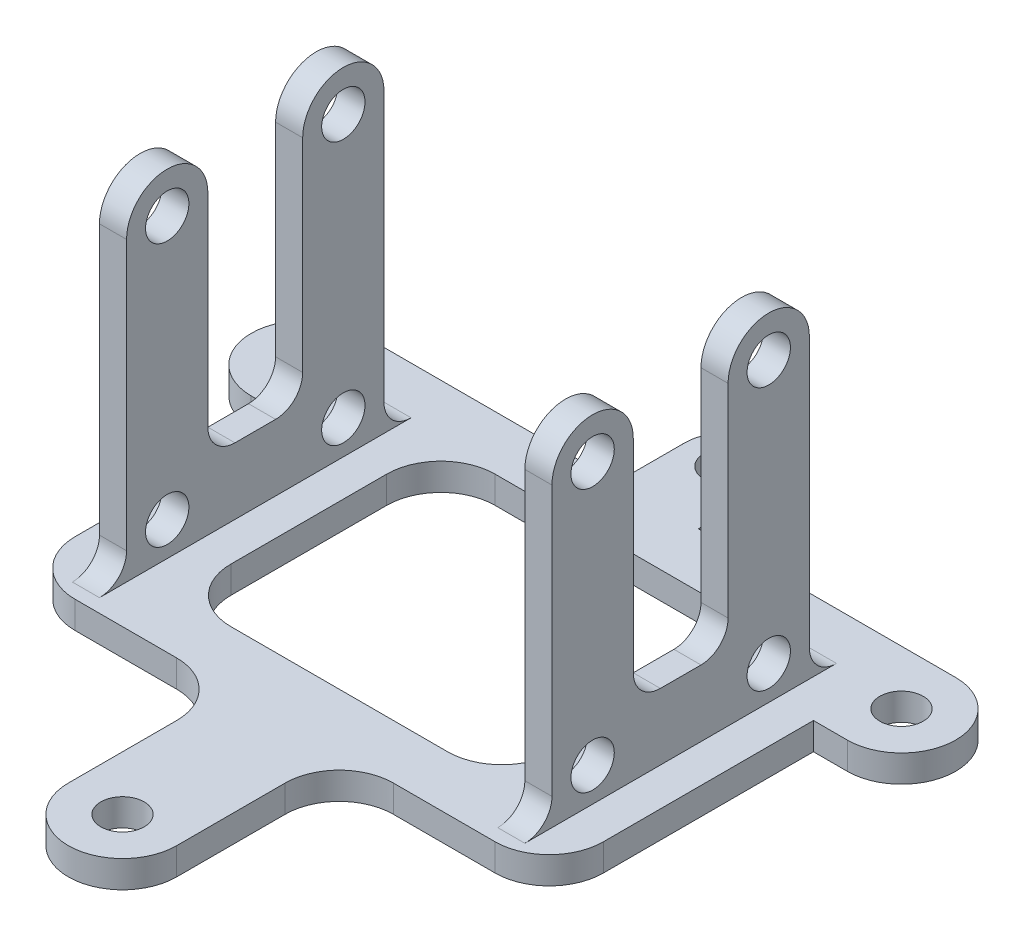
SolidWorks part; units mm, degrees
ref_plane "Front Plane" through (0, 0, 0) normal (0, 0, 1) x (1, 0, 0)
ref_plane "Top Plane" through (0, 0, 0) normal (0, 1, 0) x (1, 0, 0)
ref_plane "Right Plane" through (0, 0, 0) normal (1, 0, 0) x (0, 0, -1)
sketch "Sketch1" plane through (0, 0, 0) normal (0, 1, 0) x (1, 0, 0)
  line L2 (26, -5) -> (26, -15)
  line L3 (4, 0) -> (4, -1)
  line L4 (22, -1) -> (4, -1)
  line L5 (-4, -1) -> (-4, 0)
  line L7 (22, -19) -> (4, -19)
  line L8 (4, -30) -> (4, -19)
  line L9 (-4, -30) -> (-4, -19)
  line L10 (-22, -1) -> (-4, -1)
  line L11 (-4, 0) -> (-4, -1)
  line L12 (-26, -5) -> (-26, -15)
  line L13 (-4, -45) -> (-4, -30)
  line L14 (-22, -19) -> (-4, -19)
  line L15 (4, -1) -> (4, 0)
  line L16 (4, -45) -> (4, -30)
  line L17 (-1.6, -30) -> (-1.6, -45)
  line L19 (1.6, -30) -> (1.6, -45)
  circle A0 centre (0, 0) radius 1.6
  arc A1 (4, 0) -> (-4, 0) centre (0, 0) ccw
  circle A2 centre (22, -5) radius 1.6
  arc A3 (26, -5) -> (22, -1) centre (22, -5) ccw
  circle A4 centre (22, -15) radius 1.6
  arc A5 (22, -19) -> (26, -15) centre (22, -15) ccw
  arc A6 (1.6, -30) -> (-1.6, -30) centre (0, -30) ccw
  arc A8 (-22, -19) -> (-26, -15) centre (-22, -15) cw
  circle A9 centre (-22, -15) radius 1.6
  arc A10 (-26, -5) -> (-22, -1) centre (-22, -5) cw
  circle A11 centre (-22, -5) radius 1.6
  arc A12 (-4, -45) -> (4, -45) centre (0, -45) ccw
  arc A13 (-1.6, -45) -> (1.6, -45) centre (0, -45) ccw
extrude "Boss-Extrude1" add sketch "Sketch1" along normal blind 2 contours L13 A12 L16 L8 L7 A5 L2 A3 L4 L3 A1 L5 L10 A10 L12 A8 L14 L9 A13 L17 A6 L19 A11 A0 A2 A4 A9 region at (0, 0, 13.3577)
sketch "Sketch2" plane through (0, 2, 0) normal (0, 1, 0) x (1, 0, 0)
  line L0 (0, 0) -> (0, 3)
  line L1 (-4, 0) -> (-4, 3)
  line L2 (4, 0) -> (4, 3)
  circle A0 centre (0, 3) radius 4
  circle A1 centre (0, 0) radius 4
  circle A2 centre (0, 3) radius 1.6
extrude "Boss-Extrude3" add sketch "Sketch2" against normal up to surface (2 mm away) contours A2 A0 | A0 L2 | A0 L1 | A1 region at (-3.913, 2, -1.5) region at (0, 2, -4.7483) region at (3.913, 2, -1.5) up to face at (0, 0, 37.5)
sketch "Sketch4" plane through (0, 2, 0) normal (0, 1, 0) x (1, 0, 0)
  circle A0 centre (0, 3) radius 1.6
extrude "Cut-Extrude2" cut sketch "Sketch4" against normal blind 4
sketch "Sketch5" plane through (0, 2, 0) normal (0, 1, 0) x (1, 0, 0)
  line L0 (-4, -1) -> (4, -1)
  line L1 (-4, -1) -> (-11.9576, 14.4075)
  line L2 (-11.9576, 14.4075) -> (9.1218, 12.8952)
  line L3 (9.1218, 12.8952) -> (4, -1)
extrude "Cut-Extrude3" cut sketch "Sketch5" against normal blind 10
sketch "Sketch6" plane through (0, 2, 0) normal (0, 1, 0) x (1, 0, 0)
  line L0 (22, -1) -> (-22, -1) construction
  circle A0 centre (0, -1) radius 3
  circle A1 centre (0, -1) radius 1.6
extrude "Boss-Extrude4" add sketch "Sketch6" against normal up to surface (2 mm away) up to face at (0, 0, 37.5)
sketch "Sketch7" plane through (0, 2, 0) normal (0, 1, 0) x (1, 0, 0)
  line L0 (1.6, -1) -> (-1.6, -1) construction
  circle A0 centre (0, -1) radius 1.6
extrude "Cut-Extrude4" cut sketch "Sketch7" against normal blind 10
sketch "Sketch8" plane through (0, 2, 0) normal (0, 1, 0) x (1, 0, 0)
  line L0 (-18, -5) -> (-18, -15)
  line L1 (18, -5) -> (18, -15)
  line L2 (18, -15) -> (-18, -15)
  line L3 (-18, -5) -> (18, -5)
  circle A0 centre (-22, -5) radius 4
  circle A1 centre (-22, -15) radius 4
  circle A2 centre (22, -15) radius 4
  circle A3 centre (22, -5) radius 4
extrude "Cut-Extrude6" cut sketch "Sketch8" against normal blind 9.5 contours L3 L0 L2 L1 region at (0, 2, 10)
fillet "Fillet3" radius 3 4 edges at (18, 1, 5) (18, 1, 15) (-18, 1, 15) (-18, 1, 5)
sketch "Sketch9" plane through (0, 2, 0) normal (0, 1, 0) x (1, 0, 0)
  circle A0 centre (0, -1) radius 1.6
extrude "Boss-Extrude5" add sketch "Sketch9" against normal up to surface (2 mm away) up to face at (0, 0, 15.0714)
sketch "Sketch10" plane through (0, 2, 0) normal (0, 1, 0) x (1, 0, 0)
  line L0 (3, -1) -> (3, 3)
  line L1 (3, -1) -> (-3, -1)
  line L2 (-3, -1) -> (-3, 3)
  arc A0 (3, 3) -> (-3, 3) centre (0, 3) ccw
  circle A1 centre (0, 3) radius 1.6
extrude "Boss-Extrude6" add sketch "Sketch10" against normal up to surface (2 mm away) up to face at (0, 0, 15.0714)
sketch "Sketch11" plane through (0, 2, 0) normal (0, 1, 0) x (1, 0, 0)
  circle A0 centre (0, 3) radius 1.6
extrude "Cut-Extrude7" cut sketch "Sketch11" against normal blind 10
sketch "Sketch12" plane through (0, 2, 0) normal (0, 1, 0) x (1, 0, 0)
  line L1 (-3, 3) -> (-3, 4)
  line L3 (3, 4) -> (3, 3)
  line L4 (3, 3) -> (2.8284, 3)
  line L5 (-2.8284, 3) -> (-3, 3)
  arc A0 (-2.8284, 3) -> (2.8284, 3) centre (0, 4) ccw
  arc A1 (3, 4) -> (-3, 4) centre (0, 4) ccw
extrude "Boss-Extrude7" add sketch "Sketch12" against normal up to surface (2 mm away) up to face at (0, 0, 12.8125)
sketch "Sketch13" plane through (0, 2, 0) normal (0, 1, 0) x (1, 0, 0)
  circle A0 centre (0, 4) radius 1.6
extrude "Cut-Extrude9" cut sketch "Sketch13" against normal blind 5.5
sketch "Sketch14" plane through (0, 2, 0) normal (0, 1, 0) x (1, 0, 0)
sketch "Sketch15" plane through (0, 2, 0) normal (0, 1, 0) x (1, 0, 0)
  line L0 (-4, -45) -> (-4, -23.9538)
  line L1 (-4, -23.9538) -> (4, -23.9538)
  line L2 (4, -23.9538) -> (4, -45)
  arc A1 (-4, -45) -> (4, -45) centre (0, -45) ccw
extrude "Boss-Extrude8" add sketch "Sketch15" against normal up to surface (2 mm away) up to face at (0, 0, -2.4)
sketch "Sketch16" plane through (0, 2, 0) normal (0, 1, 0) x (1, 0, 0)
  circle A0 centre (0, -45) radius 1.6
  circle A1 centre (0, -36) radius 1.6
extrude "Cut-Extrude10" cut sketch "Sketch16" against normal blind 10
sketch "Sketch17" plane through (0, 2, 0) normal (0, 1, 0) x (1, 0, 0)
  circle A0 centre (0, -36) radius 2.8849
extrude "Boss-Extrude9" add sketch "Sketch17" against normal blind 1
sketch "Sketch18" plane through (0, 1, 0) normal (0, -1, 0) x (-1, 0, 0)
  circle A0 centre (0, -36) radius 1.6
extrude "Boss-Extrude10" add sketch "Sketch18" along normal blind 3
sketch "Sketch19" plane through (0, -2, 0) normal (0, -1, 0) x (-1, 0, 0)
  circle A0 centre (0, -36) radius 1.6
  circle A1 centre (0, -36) radius 1.5
extrude "Cut-Extrude11" cut sketch "Sketch19" against normal up to surface (2 mm away) up to face at (0, 0, 46.6)
sketch "Sketch20" plane through (0, 0, 0) normal (0, -1, 0) x (-1, 0, 0)
  circle A0 centre (0, -40.5) radius 1.6
extrude "Cut-Extrude12" cut sketch "Sketch20" against normal blind 10
sketch "Sketch21" plane through (0, 0, 0) normal (0, -1, 0) x (-1, 0, 0)
  circle A1 centre (0, -36) radius 1.5
extrude "Cut-Extrude13" cut sketch "Sketch21" along normal blind 8.5
sketch "Sketch22" plane through (0, 2, 0) normal (0, 1, 0) x (1, 0, 0)
  line L1 (-16.5, -15) -> (-16.5, -6.5)
  line L2 (-16.5, -6.5) -> (-14.6649, -6.5)
  line L3 (-14.6649, -6.5) -> (-14.6649, -25.5)
  line L4 (-14.6649, -25.5) -> (-16.5, -25.5)
  line L5 (-16.5, -25.5) -> (-16.5, -15)
  line L7 (16.5, -25.5) -> (16.5, -15)
  line L8 (14.5, -25.5) -> (16.5, -25.5)
  line L9 (14.5, -6.5) -> (14.5, -25.5)
  line L10 (16.5, -6.5) -> (14.5, -6.5)
  line L11 (16.5, -15) -> (16.5, -6.5)
extrude "Boss-Extrude12" add sketch "Sketch22" along normal blind 25 and the other way blind 2
sketch "Sketch23" plane through (16.5, 0, 0) normal (1, 0, 0) x (0, 0, -1)
  line L0 (-25.5, 2) -> (-22.5, 2)
  line L1 (-25.5, 0) -> (-25.5, 27) construction
  line L2 (-25.5, 2) -> (-25.5, 0)
  line L4 (-22.5, 2) -> (-22.5, 4.5)
  line L5 (-22.5, 4.5) -> (-22.5, 23.9)
  line L6 (-22.5, 23.9) -> (-19.5, 23.9)
  line L7 (-19.5, 23.9) -> (-19.5, 6.9)
  line L8 (-19.5, 6.9) -> (-12.5, 6.9)
  line L9 (-12.5, 6.9) -> (-12.5, 23.9)
  line L10 (-25.5, 23.9) -> (-25.5, 2)
  line L11 (-6.5, 23.9) -> (-6.6, 2)
  line L12 (-6.6, 2) -> (-22.5, 2)
  line L13 (-12.5, 23.9) -> (-9.5, 23.9)
  circle A0 centre (-22.5, 23.9) radius 3
  circle A1 centre (-9.5, 23.9) radius 3
  line M9 (-6.5, 0) -> (-6.5, 27)
  line M10 (-6.5, 27) -> (-25.5, 27)
  line M11 (-25.5, 27) -> (-25.5, 0)
extrude "Cut-Extrude14" cut sketch "Sketch23" against normal blind 48 contours A1 A0 L7 L8 L9 M9 M10 M11 region at (16.5, 17.5094, 16)
sketch "Sketch24" plane through (16.5, 0, 0) normal (1, 0, 0) x (0, 0, -1)
  circle A0 centre (-22.5, 23.9) radius 1.6
  circle A1 centre (-9.5, 23.9) radius 1.6
  circle A2 centre (-22.5, 4.5) radius 1.6
  circle A3 centre (-9.5, 4.5) radius 1.6
extrude "Cut-Extrude15" cut sketch "Sketch24" against normal blind 48
sketch "Sketch25" plane through (0, 0, 0) normal (0, -1, 0) x (-1, 0, 0)
  line L0 (14.6649, -6.5) -> (14.6649, -3.5087)
  line L1 (14.6649, -3.5087) -> (19.1284, -3.5087)
  line L2 (19.1284, -3.5087) -> (19.1284, -15.8565)
  line L3 (19.1284, -15.8565) -> (14.6649, -15.8565)
  line L4 (14.6649, -15.8565) -> (14.6649, -6.5)
  line L5 (-14.5, -6.7838) -> (-14.5, -16.6973)
  line L6 (-14.5, -6.5) -> (-14.5, -15) construction
  line L7 (-14.5, -16.6973) -> (-19.3753, -16.6973)
  line L8 (-19.3753, -16.6973) -> (-19.3753, -3.5087)
  line L9 (-19.3753, -3.5087) -> (-14.5, -3.5087)
  line L10 (-14.5, -3.5087) -> (-14.5, -6.7838)
extrude "Boss-Extrude13" add sketch "Sketch25" against normal up to surface (2 mm away) up to face at (0, 2, 8.5162)
sketch "Sketch26" plane through (0, 0, 0) normal (0, -1, 0) x (-1, 0, 0)
  line L0 (14.6649, -25.5) -> (-14.5, -25.5)
  line L1 (-14.5, -25.5) -> (-14.5, -19)
  line L2 (-14.5, -19) -> (14.6649, -19)
  line L3 (14.6649, -19) -> (14.6649, -25.5)
extrude "Boss-Extrude14" add sketch "Sketch26" against normal up to surface (2 mm away) up to face at (-0.0165, 2, 7.25)
sketch "Sketch27" plane through (0, 2, 0) normal (0, 1, 0) x (1, 0, 0)
  line L2 (4, -20.5) -> (-4, -20.5)
  line L3 (-4, -20.5) -> (-12, -20.5)
  line L4 (-12, -20.5) -> (-12, -15)
  line L5 (14.5, -15) -> (-14.6649, -15) construction
  line L6 (-12, -15) -> (4, -15)
  line L8 (4, -20.5) -> (12, -20.5)
  line L9 (12, -20.5) -> (12, -15)
  line L10 (12, -15) -> (4, -15)
extrude "Cut-Extrude16" cut sketch "Sketch27" against normal blind 48
fillet "Fillet4" radius 3 6 edges at (12, 1, 15) (-12, 1, 15) (-4, 1, 25.5) (4, 1, 25.5) (16.5, 1, 19) (-16.5, 1, 19)
sketch "Sketch28" plane through (0, 2, 0) normal (0, 1, 0) x (1, 0, 0)
  line L0 (-4, -40.5) -> (-24.8349, -51.1299)
  line L1 (-24.8349, -51.1299) -> (5.5059, -58.3772)
  line L2 (5.5059, -58.3772) -> (27.5856, -52.632)
  line L3 (27.5856, -52.632) -> (27.5856, -52.2189)
  line L4 (27.5856, -52.2189) -> (4, -40.5)
  circle A0 centre (0, -40.5) radius 4
  line M11 (-4, -28.5) -> (-4, -45)
  arc M12 (-4, -45) -> (4, -45) centre (0, -45) ccw
  line M13 (4, -45) -> (4, -28.5)
  circle M16 centre (0, -45) radius 1.6
extrude "Cut-Extrude17" cut sketch "Sketch28" against normal blind 48 contours L3 L4 L0 L1 L2 M13 M12 M11 | A0 M16 M11 M12 M13 region at (1.9393, 2, 50.4083) region at (-3.3853, 2, 42.8425)
sketch "Sketch29" plane through (0, 2, 0) normal (0, 1, 0) x (1, 0, 0)
  circle A0 centre (0, -40.5) radius 1.6
  circle A1 centre (0, -40.5) radius 4
extrude "Boss-Extrude15" add sketch "Sketch29" against normal up to surface (2 mm away) up to face at (0, 0, -2.4)
fillet "Fillet5" radius 3 2 edges at (-14.6649, 1, 15) (14.5, 1, 15)
sketch "Sketch30" plane through (0, 2, 0) normal (0, 1, 0) x (1, 0, 0)
  line L0 (-12, -20.5) -> (-12, -5)
  line L1 (-14.6649, -5) -> (14.5, -5) construction
  line L2 (-12, -5) -> (12, -20.5)
  line L3 (12, -20.5) -> (12, -5)
  line L4 (12, -5) -> (14.5, -5)
  line L5 (14.5, -5) -> (14.5, -20.5)
  line L6 (14.5, -19.5) -> (14.5, -25.5) construction
  line L7 (14.5, -20.5) -> (12, -20.5)
  line L8 (-12, -5) -> (-14.6649, -5)
  line L9 (-14.6649, -5) -> (-14.6649, -20.5)
  line L10 (-14.6649, -25.5) -> (-14.6649, -19.5) construction
  line L11 (-14.6649, -20.5) -> (-12, -20.5)
  line M1 (-4, -28.5) -> (-4, -40.5)
  arc M2 (-4, -40.5) -> (4, -40.5) centre (0, -40.5) ccw
  line M3 (4, -40.5) -> (4, -28.5)
  arc M4 (4, -28.5) -> (7, -25.5) centre (7, -28.5) cw
  line M5 (7, -25.5) -> (14.5, -25.5)
  line M6 (14.5, -25.5) -> (14.5, -13.0846)
  arc M7 (14.5, -13.0846) -> (13.25, -15.5213) centre (11.5, -13.0846) cw
  arc M8 (13.25, -15.5213) -> (12, -17.958) centre (15, -17.958) ccw
  line M10 (12, -20.5) -> (-12, -20.5)
  arc M12 (-12, -17.9812) -> (-13.3324, -15.4874) centre (-15, -17.9812) ccw
  arc M13 (-13.3324, -15.4874) -> (-14.6649, -12.9935) centre (-11.6649, -12.9935) cw
  line M14 (-14.6649, -12.9935) -> (-14.6649, -25.5)
  line M15 (-14.6649, -25.5) -> (-7, -25.5)
  arc M16 (-7, -25.5) -> (-4, -28.5) centre (-7, -28.5) cw
  circle M17 centre (0, -40.5) radius 1.6
extrude "Boss-Extrude16" add sketch "Sketch30" against normal up to surface (2 mm away) contours L8 L9 L0 M13 M12 | L5 L4 L3 M8 M7 | L11 L7 M14 M15 M16 M1 M2 M3 M4 M5 M6 M10 M17 region at (-0.0419, 2, 28.4188) region at (-13.2651, 2, 10.2855) region at (13.188, 2, 10.301) up to face at (0, 0, -2.4)
sketch "Sketch31" plane through (0, 2, 0) normal (0, 1, 0) x (1, 0, 0)
  line L0 (-19.5, -19) -> (-19.5, -28.5)
  line L1 (-19.5, -28.5) -> (-4, -28.5)
  line L2 (-4, -28.5) -> (-4, -20.5)
  line L3 (-12, -20.5) -> (12, -20.5) construction
  line L4 (-4, -20.5) -> (-14.6649, -20.5)
  line L5 (-14.6649, -25.5) -> (-14.6649, -6.5) construction
  line L6 (-14.6649, -20.5) -> (-14.6649, -19)
  line L7 (-14.6649, -19.5) -> (-14.6649, -12.5) construction
  line L8 (-14.6649, -19) -> (-19.5, -19)
  line L10 (14.5, -19) -> (19.5, -19)
  line L11 (14.5, -20.5) -> (14.5, -19)
  line L12 (4, -20.5) -> (14.5, -20.5)
  line L13 (4, -28.5) -> (4, -20.5)
  line L14 (19.5, -28.5) -> (4, -28.5)
  line L15 (19.5, -19) -> (19.5, -28.5)
extrude "Boss-Extrude17" add sketch "Sketch31" against normal up to surface (2 mm away) up to face at (0, 0, 12.75)
sketch "Sketch34" plane through (0, 0, 0) normal (0, -1, 0) x (1, 0, 0)
  line L0 (-19.5, 19) -> (-19.5, 9)
  line L2 (19.5, 19) -> (19.5, 9)
  line L4 (-22, 9) -> (-19.5, 9)
  line L6 (26, 5) -> (32.3656, 16.2838)
  line L7 (32.3656, 16.2838) -> (22.3704, 25.2129)
  line L8 (22.3704, 25.2129) -> (19.5, 19)
  line L9 (-26, 5) -> (-35.1133, 22.6363)
  line L10 (-35.1133, 22.6363) -> (-23.2967, 23.1694)
  line L11 (-23.2967, 23.1694) -> (-19.5, 19)
  line L12 (19.5, 9) -> (22, 9)
  arc A0 (-22, 9) -> (-26, 5) centre (-22, 5) ccw
  arc A1 (26, 5) -> (22, 9) centre (22, 5) ccw
extrude "Cut-Extrude18" cut sketch "Sketch34" against normal blind 10
fillet "Fillet6" radius 4 8 edges at (12, 1, 5) (-12, 1, 5) (-12, 1, 20.5) (12, 1, 20.5) (4, 1, 28.5) (19.5, 1, 28.5) (-4, 1, 28.5) (-19.5, 1, 28.5)
fillet "Fillet7" radius 2 8 edges at (15.5, 6.9, 12.5) (15.5, 6.9, 19.5) (-15.5824, 6.9, 19.5) (-15.5824, 6.9, 12.5) (15.5, 2, 6.5) (15.5, 2, 25.5) (-15.5824, 2, 25.5) (-15.5824, 2, 6.5)
sketch "Sketch35" plane through (0, 2, 0) normal (0, 1, 0) x (1, 0, 0)
  line L1 (12, -16.5) -> (12, -24.5)
  line L2 (12, -16.5) -> (12, -9) construction
  line L3 (12, -24.5) -> (-12, -24.5)
  line L4 (-12, -16.5) -> (-12, -24.5)
  line L5 (-12, -16.5) -> (12, -16.5)
  arc A0 (8, -20.5) -> (12, -16.5) centre (8, -16.5) ccw construction
extrude "Cut-Extrude19" cut sketch "Sketch35" against normal blind 10
fillet "Fillet8" radius 4 2 edges at (12, 1, 24.5) (-12, 1, 24.5)
sketch "Sketch37" plane through (16.5, 0, 0) normal (1, 0, 0) x (0, 0, -1)
  line L0 (-27.5, 2) -> (-4.5, 2)
  line L1 (-6.5, 4) -> (-6.5, 23.9)
  line L2 (-12.5, 23.9) -> (-12.5, 8.9)
  line L3 (-14.5, 6.9) -> (-17.5, 6.9)
  line L4 (-19.5, 8.9) -> (-19.5, 23.9)
  line L5 (-25.5, 23.9) -> (-25.5, 4)
  arc A0 (-12.5, 23.9) -> (-6.5, 23.9) centre (-9.5, 23.9) cw
  arc A1 (-6.5, 23.9) -> (-12.5, 23.9) centre (-9.5, 23.9) ccw construction
  arc A2 (-6.5, 4) -> (-4.5, 2) centre (-4.5, 4) ccw
  arc A3 (-25.5, 4) -> (-27.5, 2) centre (-27.5, 4) cw
  arc A4 (-25.5, 23.9) -> (-19.5, 23.9) centre (-22.5, 23.9) cw
  arc A5 (-19.5, 8.9) -> (-17.5, 6.9) centre (-17.5, 8.9) ccw
  arc A6 (-14.5, 6.9) -> (-12.5, 8.9) centre (-14.5, 8.9) ccw
  circle A7 centre (-22.5, 23.9) radius 1.6
  circle A8 centre (-9.5, 23.9) radius 1.6
  circle A9 centre (-9.5, 4.5) radius 1.6
  circle A10 centre (-22.5, 4.5) radius 1.6
extrude "Boss-Extrude18" add sketch "Sketch37" along normal blind 0.2 and the other way blind 33.2
sketch "Sketch38" plane through (0, 0, 25.5) normal (0, 0, 1) x (1, 0, 0)
  line L0 (-16.7, 13.95) -> (-14.7, 13.95)
  line L1 (-16.7, 23.9) -> (-16.7, 4) construction
  line L2 (-14.7, 13.95) -> (-14.7, 2)
  line L3 (-15.5, 2) -> (-8, 2) construction
  line L4 (-14.7, 2) -> (14.7, 2)
  line L5 (8, 2) -> (15.5, 2) construction
  line L6 (14.7, 2) -> (14.7, 32.1024)
  line L7 (14.7, 32.1024) -> (-14.7, 32.1024)
  line L8 (-14.7, 32.1024) -> (-14.7, 13.95)
  line L9 (16.7, 13.95) -> (14.7, 13.95)
  line L10 (16.7, 23.9) -> (16.7, 4) construction
  line M3 (16.7, 23.9) -> (-16.7, 23.9)
  line M5 (-16.7, 4) -> (16.7, 4)
extrude "Cut-Extrude20" cut sketch "Sketch38" against normal blind 31.2 and the other way blind 10 contours L8 L2 L6 M3 M5 | L7 L8 L6 M3 | L4 L6 L2 M5 region at (0, 13.95, 25.5) region at (0, 3, 25.5) region at (0, 28.0012, 25.5)
